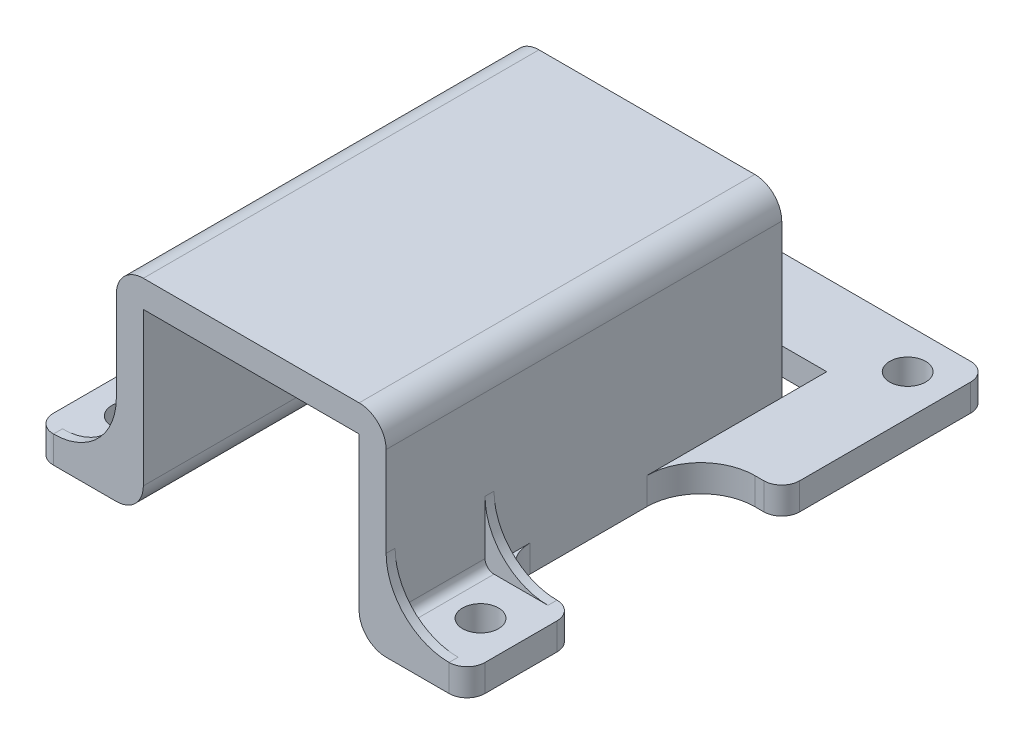
SolidWorks part; units mm, degrees
other "Camera1"
ref_plane "Front Plane" through (0, 0, 0) normal (0, 0, 1) x (1, 0, 0)
ref_plane "Top Plane" through (0, 0, 0) normal (0, 1, 0) x (1, 0, 0)
ref_plane "Right Plane" through (0, 0, 0) normal (1, 0, 0) x (0, 0, -1)
sketch "Sketch2" plane through (0, 0, 0) normal (0, 0, 1) x (1, 0, 0)
  line L0 (0, 0) -> (4.5, 0)
  line L1 (6, 1.5) -> (6, 10)
  line L2 (6, 10) -> (18, 10)
  line L3 (18, 10) -> (18, 1.5)
  line L4 (19.5, 0) -> (24, 0)
  line L5 (0, 0) -> (0, 1.5)
  line L6 (0, 1.5) -> (1, 1.5)
  line L7 (4.5, 5) -> (4.5, 10)
  line L8 (6, 11.5) -> (18, 11.5)
  line L9 (19.5, 10) -> (19.5, 5)
  line L10 (23, 1.5) -> (24, 1.5)
  line L11 (24, 1.5) -> (24, 0)
  line L12 (4.5, 0) -> (4.5, 5)
  line L13 (19.5, 0) -> (19.5, 5)
  arc A0 (18, 1.5) -> (19.5, 0) centre (19.5, 1.5) ccw
  arc A1 (4.5, 0) -> (6, 1.5) centre (4.5, 1.5) ccw
  arc A2 (19.5, 10) -> (18, 11.5) centre (18, 10) ccw
  arc A3 (4.5, 10) -> (6, 11.5) centre (6, 10) cw
  arc A4 (23, 1.5) -> (19.5, 5) centre (23, 5) cw
  arc A5 (4.5, 5) -> (1, 1.5) centre (1, 5) cw
  point P17 (18, 0)
  point P20 (6, 0)
  dimension "D10" = 1.5
  dimension "D11" = 3.5
  dimension "D1" = 6
  dimension "D2" = 10
  dimension "D3" = 12
  dimension "D4" = 6
  dimension "D5" = 1.5
  dimension "D6" = 1.5
  dimension "D7" = 1.5
  dimension "D8" = 1.5
  dimension "D9" = 1.5
extrude "Boss-Extrude1" add sketch "Sketch2" against normal blind 22 contours A3 L7 A1 L1 L2 L3 A0 L9 A2 L8 region at (4.689, 2.5, 0)
extrude "Boss-Extrude2" add sketch "Sketch2<6>" against normal blind 6 contours L12 A5 L6 L5 L0 | L10 A4 L13 L4 L11 region at (2.6615, 1.1794, 0) region at (21.3385, 1.1794, 0)
sketch "Sketch2<6>" plane through (0, 0, 0) normal (0, 0, 1) x (1, 0, 0) same geometry as "Sketch2"
sketch "Sketch3" plane through (0, 1.5, 0) normal (0, 1, 0) x (1, 0, 0)
  line L0 (24, 3) -> (24, 5.5)
  line L1 (24, 6) -> (24, 0) construction
  line L2 (24, 5.5) -> (19.5, 5.5)
  line L3 (19.5, 6) -> (19.5, 0) construction
  line L4 (19.5, 5.5) -> (19.5, 0.5)
  line L5 (19.5, 0.5) -> (24, 0.5)
  line L6 (24, 0.5) -> (24, 3)
  line L7 (0, 3) -> (0, 0.5)
  line L8 (0, 6) -> (0, 0) construction
  line L9 (0, 0.5) -> (4.5, 0.5)
  line L10 (4.5, 0.5) -> (4.5, 5.5)
  line L11 (4.5, 5.5) -> (0, 5.5)
  line L12 (0, 5.5) -> (0, 3)
  dimension "D1" = 2.5
  dimension "D2" = 2.5
  dimension "D3" = 4.5
  dimension "D4" = 5
  dimension "D5" = 2.5
extrude "Cut-Extrude1" cut sketch "Sketch3" along normal blind 6
fillet "Fillet1" radius 0.5 2 edges at (19.5, 1.5, -3) (4.5, 1.5, -3)
sketch "Sketch4" plane through (0, 1.5, 0) normal (0, 1, 0) x (1, 0, 0)
  line L0 (0, 3) -> (2.25, 3) construction
  line L1 (0, 6) -> (0, 0) construction
  line L2 (12, 0) -> (12, 22) construction
  line L3 (6, 0) -> (18, 0) construction
  line L4 (6, 22) -> (18, 22) construction
  circle A0 centre (2.25, 3) radius 1.0007
  circle A1 centre (21.75, 3) radius 1.0007
  dimension "D2" = 2.0013
  dimension "D1" = 2.25
extrude "Cut-Extrude2" cut sketch "Sketch4" against normal blind 6
sketch "Sketch5" plane through (0, 0, -22) normal (0, 0, -1) x (-1, 0, 0)
  line L1 (-24, 1.5) -> (-19.5, 1.5)
  line L2 (-24, 1.5) -> (-24, 0)
  line L3 (-24, 0) -> (-19.5, 0)
  line L4 (-19.5, 1.5) -> (-19.5, 0)
  line L5 (0, 1.5) -> (-4.5, 1.5)
  line L6 (0, 1.5) -> (0, 0)
  line L7 (0, 0) -> (-4.5, 0)
  line L8 (-4.5, 1.5) -> (-4.5, 0)
extrude "Boss-Extrude3" add sketch "Sketch5" against normal blind 4.5
sketch "Sketch7" plane through (0, 0, -22) normal (0, 0, -1) x (-1, 0, 0)
  line L1 (-19.5, 1.5) -> (-24, 1.5)
  line L2 (-19.5, 1.5) -> (-19.5, 0)
  line L3 (-19.5, 0) -> (-24, 0)
  line L4 (-24, 1.5) -> (-24, 0)
  line L5 (0, 1.5) -> (-4.5, 1.5)
  line L6 (0, 1.5) -> (0, 0)
  line L7 (0, 0) -> (-4.5, 0)
  line L8 (-4.5, 1.5) -> (-4.5, 0)
extrude "Boss-Extrude4" add sketch "Sketch7" along normal blind 7
sketch "Sketch8" plane through (4.5, 0, 0) normal (1, 0, 0) x (0, 0, -1)
  line L0 (29, 0) -> (22, 0) construction
  line L1 (29, 1.5) -> (24.5, 1.5)
  line L2 (29, 1.5) -> (29, 0)
  line L3 (29, 0) -> (24.5, 0)
  line L4 (24.5, 1.5) -> (24.5, 0)
  dimension "D1" = 4.5
extrude "Boss-Extrude5" add sketch "Sketch8" along normal blind 17
sketch "Sketch9" plane through (0, 1.5, 0) normal (0, 1, 0) x (1, 0, 0)
  line L0 (12, 29) -> (12, 24.5) construction
  line L1 (0, 29) -> (2.25, 29) construction
  line L2 (0, 29) -> (0, 26.75) construction
  line L3 (0, 26.75) -> (2.25, 26.75) construction
  line L4 (2.25, 29) -> (2.25, 26.75) construction
  line L5 (0, 29) -> (24, 29) construction
  line L6 (19.5, 24.5) -> (4.5, 24.5) construction
  circle A0 centre (2.25, 26.75) radius 1
  circle A1 centre (21.75, 26.75) radius 1
  dimension "D3" = 2
  dimension "D1" = 2.25
  dimension "D2" = 2.25
extrude "Cut-Extrude3" cut sketch "Sketch9" against normal blind 17
fillet "Fillet2" radius 1 8 edges at (24, 0.75, 0) (0, 0.75, 0) (0, 0.75, -6) (24, 0.75, -6) (24, 0.75, -17.5) (24, 0.75, -29) (0, 0.75, -17.5) (0, 0.75, -29)
fillet "Fillet3" radius 3 2 edges at (19.5, 0.75, -17.5) (4.5, 0.75, -17.5)
sketch "Sketch13" plane through (0, 0, 0) normal (0, -1, 0) x (1, 0, 0)
  line L0 (2.5, -6) -> (2.2913, -6)
  line L1 (1, -6) -> (4.5, -6) construction
  line L2 (4.5, -8) -> (4.5, -9.217)
  line L3 (4.5, -14.5) -> (4.5, -6) construction
  line L4 (19.5, -8) -> (19.5, -10.8489)
  line L5 (19.5, -14.5) -> (19.5, -6) construction
  line L6 (21.5, -6) -> (22.5968, -6)
  line L7 (19.5, -6) -> (23, -6) construction
  line L8 (4.5, -6) -> (2.2913, -6)
  line L9 (4.5, -6) -> (4.5, -8)
  line L10 (21.5, -6) -> (19.5, -6)
  line L11 (19.5, -6) -> (19.5, -8)
  arc A0 (2.5, -6) -> (4.5, -8) centre (2.5, -8) cw
  arc A1 (19.5, -8) -> (21.5, -6) centre (21.5, -8) cw
  point P10 (4.5, -6)
  point P22 (19.5, -6)
  line M6 (1, -6) -> (4.5, -6)
  dimension "D1" = 2
  dimension "D2" = 2
extrude "Boss-Extrude6" add sketch "Sketch13" against normal blind 1.5 contours L11 A1 L10 | A0 L9 M6 region at (4.0533, 0, -6.4467) region at (19.9467, 0, -6.4467)
